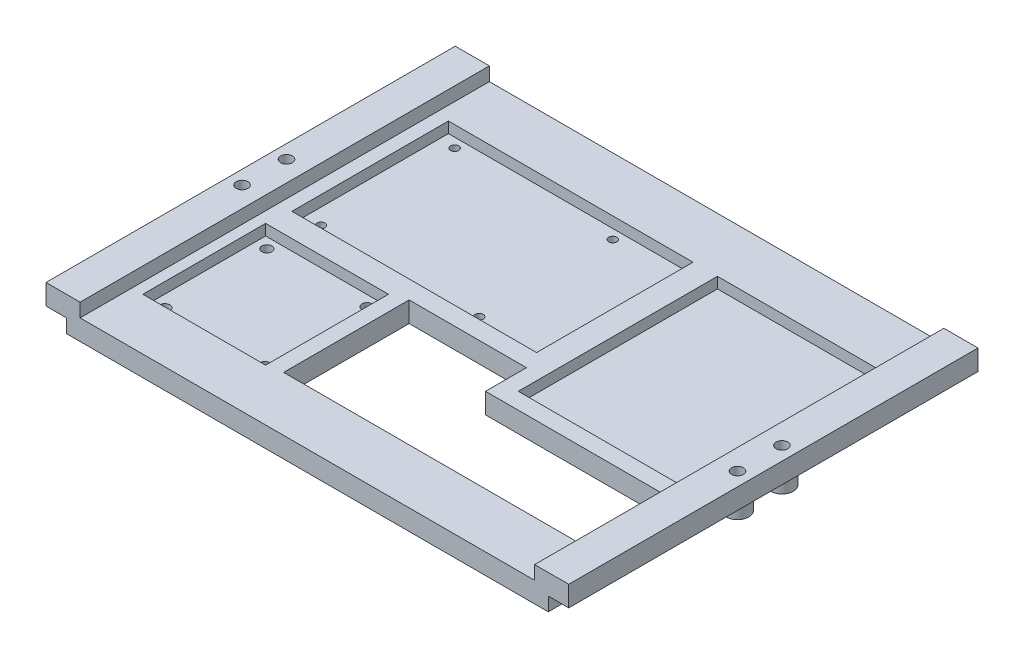
SolidWorks part; units mm, degrees
ref_plane "Front Plane" through (0, 0, 0) normal (0, 0, 1) x (1, 0, 0)
ref_plane "Top Plane" through (0, 0, 0) normal (0, 1, 0) x (1, 0, 0)
ref_plane "Right Plane" through (0, 0, 0) normal (1, 0, 0) x (0, 0, -1)
sketch "Sketch2" plane through (0, 0, 0) normal (0, 0, 1) x (1, 0, 0)
  line L0 (179.1, 12.5) -> (191.6, 12.5)
  line L1 (7.5, 0) -> (184.1, 0)
  line L2 (0, 5) -> (0, 12.5)
  line L3 (0, 12.5) -> (12.5, 12.5)
  line L4 (191.6, 5) -> (191.6, 12.5)
  line L7 (0, 5) -> (7.5, 5)
  line L8 (7.5, 0) -> (7.5, 5)
  line L11 (191.6, 5) -> (184.1, 5)
  line L12 (184.1, 0) -> (184.1, 5)
  line L14 (12.5, 12.5) -> (12.5, 7.5)
  line L15 (12.5, 7.5) -> (179.1, 7.5)
  line L16 (179.1, 12.5) -> (179.1, 7.5)
  dimension "D1" = 191.6
  dimension "D2" = 5
  dimension "D3" = 5
  dimension "D4" = 5
  dimension "D5" = 12.5
  dimension "D6" = 7.5
  dimension "D7" = 7.5
  dimension "D8" = 12.5
  dimension "D9" = 12.5
extrude "PlateFrame" add sketch "Sketch2" along normal blind 150
sketch "Sketch3" plane through (0, 12.5, 0) normal (0, 1, 0) x (1, 0, 0)
  line L0 (12.5, 0) -> (0, 0) construction
  line L2 (0, -150) -> (0, 0) construction
  line L3 (191.6, -150) -> (191.6, 0) construction
  line L4 (191.6, 0) -> (179.1, 0) construction
  circle A0 centre (5, -66.85) radius 2.15
  circle A1 centre (5, -83.15) radius 2.15
  circle A2 centre (186.6, -66.85) radius 2.15
  circle A3 centre (186.6, -83.15) radius 2.15
  dimension "D1" = 4.3
  dimension "D2" = 4.3
  dimension "D3" = 4.3
  dimension "D4" = 4.3
  dimension "D5" = 66.85
  dimension "D6" = 16.3
  dimension "D7" = 5
  dimension "D8" = 5
  dimension "D9" = 5
  dimension "D10" = 181.6
  dimension "D11" = 66.85
  dimension "D12" = 16.3
extrude "HoleSupport" cut sketch "Sketch3" against normal blind 7.5
sketch "Sketch4" plane through (0, 12.5, 0) normal (0, 1, 0) x (1, 0, 0)
  circle A0 centre (5, -66.85) radius 2.15
  circle A1 centre (5, -83.15) radius 2.15
  circle A2 centre (186.6, -83.15) radius 2.15
  circle A3 centre (186.6, -66.85) radius 2.15
  circle A4 centre (186.6, -66.85) radius 4.15
  circle A5 centre (186.6, -83.15) radius 4.15
  circle A6 centre (5, -66.85) radius 4.15
  circle A7 centre (5, -83.15) radius 4.15
  dimension "D1" = 2
extrude "CylindricalSupports" add sketch "Sketch4" against normal blind 12.5
sketch "Sketch5" plane through (0, 7.5, 0) normal (0, 1, 0) x (1, 0, 0)
  line L0 (12.5, -150) -> (12.5, 0) construction
  line L1 (17.5, -87) -> (60.5, -87)
  line L2 (12.5, -150) -> (12.5, 0) construction
  line L3 (17.5, -20) -> (107.15, -20)
  line L4 (17.5, -20) -> (17.5, -77.35)
  line L5 (17.5, -77.35) -> (107.15, -77.35)
  line L6 (107.15, -20) -> (107.15, -77.35)
  line L7 (174.1, -20) -> (116.1, -20)
  line L8 (174.1, -20) -> (174.1, -93)
  line L9 (174.1, -93) -> (116.1, -93)
  line L10 (116.1, -20) -> (116.1, -93)
  line L15 (179.1, -150) -> (179.1, 0) construction
  line L16 (179.1, 0) -> (12.5, 0) construction
  line L17 (17.5, -87) -> (17.5, -130)
  line L18 (17.5, -130) -> (60.5, -130)
  line L19 (60.5, -87) -> (60.5, -130)
  line L20 (179.1, -150) -> (12.5, -150) construction
  dimension "D1" = 5
  dimension "D2" = 89.65
  dimension "D3" = 57.35
  dimension "D4" = 5
  dimension "D5" = 43
  dimension "D6" = 58
  dimension "D7" = 43
  dimension "D8" = 20
  dimension "D9" = 20
  dimension "D10" = 5
  dimension "D11" = 73
  dimension "D12" = 20
extrude "ItemLayout" cut sketch "Sketch5" against normal blind 4
sketch "Sketch6" plane through (0, 7.5, 0) normal (0, 1, 0) x (1, 0, 0)
  line L1 (67.1, -84) -> (110.1, -84)
  line L2 (67.1, -84) -> (67.1, -130)
  line L3 (67.1, -130) -> (110.1, -130)
  line L4 (110.1, -84) -> (110.1, -99)
  line L9 (179.1, -150) -> (179.1, 0) construction
  line L10 (110.1, -130) -> (174.1, -130)
  line L12 (110.1, -99) -> (174.1, -99)
  line L13 (174.1, -130) -> (174.1, -99)
  line L14 (116.1, -93) -> (174.1, -93) construction
  line L15 (116.1, -20) -> (116.1, -93) construction
  line L17 (179.1, -150) -> (12.5, -150) construction
  dimension "D1" = 20
  dimension "D2" = 43
  dimension "D3" = 5
  dimension "D4" = 6
  dimension "D5" = 6
  dimension "D6" = 15
extrude "HoleCutout" cut sketch "Sketch6" against normal blind 7.5
sketch "Sketch7" plane through (0, 3.5, 0) normal (0, 1, 0) x (1, 0, 0)
  line L0 (17.5, -20) -> (17.5, -77.35) construction
  line L1 (17.5, -20) -> (17.5, -77.35) construction
  line L2 (107.15, -20) -> (17.5, -20) construction
  line L3 (107.15, -20) -> (17.5, -20) construction
  circle A0 centre (23.26, -23.5) radius 1.5
  circle A1 centre (23.26, -72.5) radius 1.5
  circle A2 centre (81.26, -72.5) radius 1.5
  circle A3 centre (81.26, -23.5) radius 1.5
  dimension "D1" = 3
  dimension "D2" = 3
  dimension "D3" = 3
  dimension "D4" = 3
  dimension "D5" = 5.76
  dimension "D6" = 5.76
  dimension "D7" = 3.5
  dimension "D8" = 3.5
  dimension "D9" = 58
  dimension "D10" = 58
  dimension "D11" = 49
  dimension "D12" = 49
extrude "HoleRaspberryPi" cut sketch "Sketch7" against normal blind 3.5
sketch "Sketch8" plane through (0, 3.5, 0) normal (0, 1, 0) x (1, 0, 0)
  line L0 (17.5, -130) -> (60.5, -130) construction
  line L1 (60.5, -87) -> (17.5, -87) construction
  line L2 (60.5, -130) -> (60.5, -87) construction
  line L3 (60.5, -130) -> (60.5, -87) construction
  line L4 (17.5, -87) -> (17.5, -130) construction
  line L5 (17.5, -130) -> (60.5, -130) construction
  circle A0 centre (57.56, -127.24) radius 1.85
  circle A1 centre (57.56, -89.86) radius 1.85
  circle A2 centre (20.81, -89.86) radius 1.85
  circle A3 centre (20.81, -127.24) radius 1.85
  dimension "D1" = 3.7
  dimension "D2" = 3.7
  dimension "D3" = 3.7
  dimension "D4" = 3.7
  dimension "D6" = 2.86
  dimension "D8" = 2.94
  dimension "D9" = 2.86
  dimension "D10" = 3.31
  dimension "D11" = 2.76
  dimension "D12" = 3.31
  dimension "D5" = 2.76
  dimension "D7" = 2.94
extrude "HoleMotorDriver" cut sketch "Sketch8" against normal blind 3.5
sketch "Sketch10" plane through (0, 7.5, 0) normal (0, 1, 0) x (1, 0, 0)
  line L1 (17.5, -87) -> (60.5, -87)
  line L2 (17.5, -87) -> (17.5, -130)
  line L3 (17.5, -130) -> (60.5, -130)
  line L4 (60.5, -87) -> (60.5, -130)
  line L5 (16.5, -86) -> (61.5, -86)
  line L6 (16.5, -86) -> (16.5, -131)
  line L7 (16.5, -131) -> (61.5, -131)
  line L8 (61.5, -86) -> (61.5, -131)
  dimension "D1" = 1
  dimension "D2" = 1
  dimension "D3" = 1
  dimension "D4" = 1
extrude "CutMotorDriver" cut sketch "Sketch10" against normal blind 4
